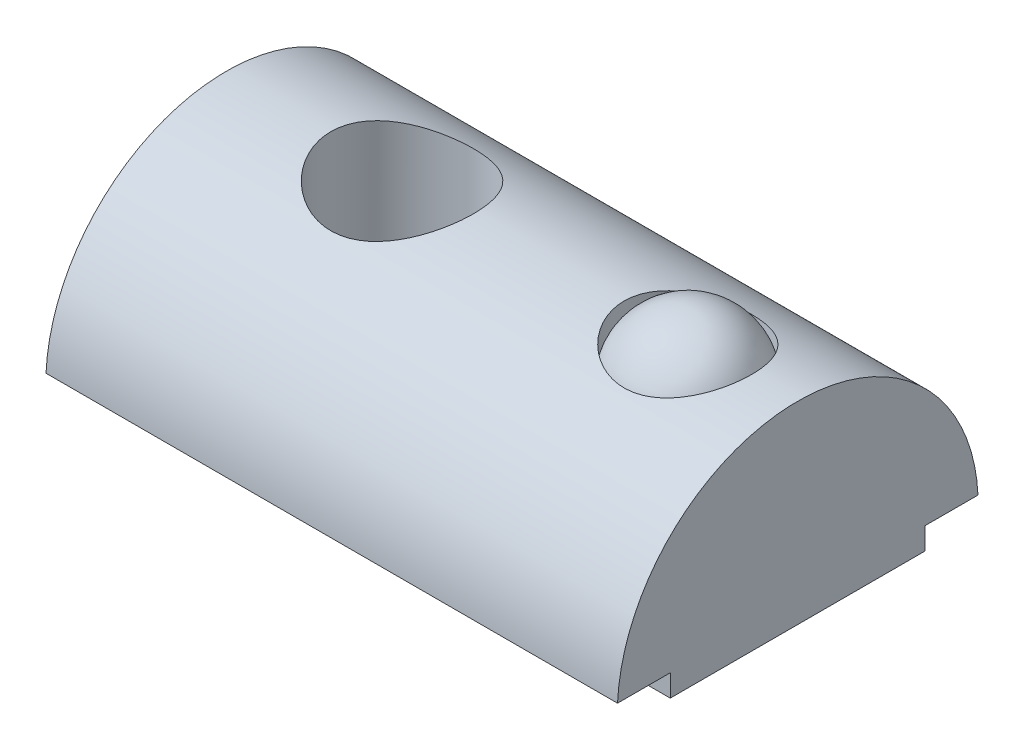
SolidWorks part; units mm, degrees
ref_plane "Front Plane" through (0, 0, 0) normal (0, 0, 1) x (1, 0, 0)
ref_plane "Top Plane" through (0, 0, 0) normal (0, 1, 0) x (1, 0, 0)
ref_plane "Right Plane" through (0, 0, 0) normal (1, 0, 0) x (0, 0, -1)
ref_axis "Axis_X" through (-4.65, 0, 0) along (1, 0, 0)
ref_axis "Axis_Y" through (0, 5.25, 0) along (0, -1, 0)
ref_axis "Axis_Z" through (0, 0, -4.51) along (0, 0, 1)
ref_plane "Plane1" through (-4, 0, 0) normal (1, 0, 0) x (0, 0, -1)
sketch "Sketch1" plane through (-4, 0, 0) normal (1, 0, 0) x (0, 0, -1)
  line L0 (4.1, 0.5) -> (2.9, 0.5)
  line L1 (0, 0) -> (0, 4.4) construction
  line L2 (2.9, 0.5) -> (2.9, 0)
  line L3 (2.9, 0) -> (-2.9, 0)
  line L4 (-2.9, 0) -> (-2.9, 0.5)
  line L5 (-2.9, 0.5) -> (-4.1, 0.5)
  arc A0 (4.1, 0.5) -> (-4.1, 0.5) centre (0, 0.2949) ccw
  dimension "B" = 8.2
  dimension "A" = 5.8
  dimension "T" = 4.4
  dimension "KSS_1" = 0.5
extrude "Boss-Extrude1" add sketch "Sketch1" along normal blind 13
hole_wizard "Tap1" positions "Sketch3" profile "Sketch2" hole size "M4x0.7" standard "JIS" end condition through all
sketch "Sketch3" plane through (0, 0, 0) normal (0, -1, 0) x (-1, 0, 0)
  point P0 (0, 0)
cosmetic thread "Thread1" parameters "M"=4
sketch "Sketch2" plane through (0, 0, 0) normal (1, 0, 0) x (0, 0, -1)
  line L0 (0, 0) -> (0, 4.4)
  line L1 (0, 4.4) -> (1.621, 4.4)
  line L2 (1.621, 4.4) -> (1.621, 0)
  line L5 (1.621, 0) -> (0, 0)
  line L11 (0, -6.35) -> (0, 107.95) construction
  dimension "HSD_1" = 3.242
  dimension "Thru Hole Depth" = 4.4
hole_wizard "DiameterHole1" positions "Sketch6" profile "Sketch5" hole size "Ø2.9" standard "JIS" end condition through all
sketch "Sketch6" plane through (0, 0, 0) normal (0, -1, 0) x (-1, 0, 0)
  circle A0 centre (0, 0) radius 1.621 construction
  point P0 (-6.5, 0)
  dimension "MSM_2" = 6.5
sketch "Sketch5" plane through (6.5, 0, 0) normal (1, 0, 0) x (0, 0, -1)
  line L0 (0, 0) -> (0, 4.4)
  line L1 (0, 4.4) -> (1.45, 4.4)
  line L2 (1.45, 4.4) -> (1.45, 0)
  line L5 (1.45, 0) -> (0, 0)
  line L11 (0, -6.35) -> (0, 107.95) construction
  dimension "HD_1" = 2.9
  dimension "Thru Hole Depth" = 4.4
sketch "Sketch4" plane through (0, 0, 0) normal (0, 0, -1) x (-1, 0, 0)
  line L0 (-6.5, 5) -> (-6.5, 2)
  line L1 (-6.5, 5) -> (-6.5, 2) construction
  line L2 (-9, 0) -> (4, 0) construction
  circle A0 centre (-6.5, 3.5) radius 1.5 construction
  arc A1 (-6.5, 5) -> (-6.5, 2) centre (-6.5, 3.5) cw
  point P2 (-6.5, 2)
  dimension "MSM_3" = 3
  dimension "E" = 5
  dimension "MSM_2" = 6.5
revolve "Revolve1" add sketch "Sketch4" angle 360 about L1
sketch "Sketch7" plane through (0, 0, 0) normal (0, -1, 0) x (1, 0, 0)
  circle A0 centre (6.5, 0) radius 1.45
  circle A1 centre (6.5, 0) radius 1.45 construction
extrude "Boss-Extrude2" add sketch "Sketch7" against normal up to next
equation "\"KSS_1\"= IIF ( \"T\" < = 5 , 0.5 , 0.8 )"
